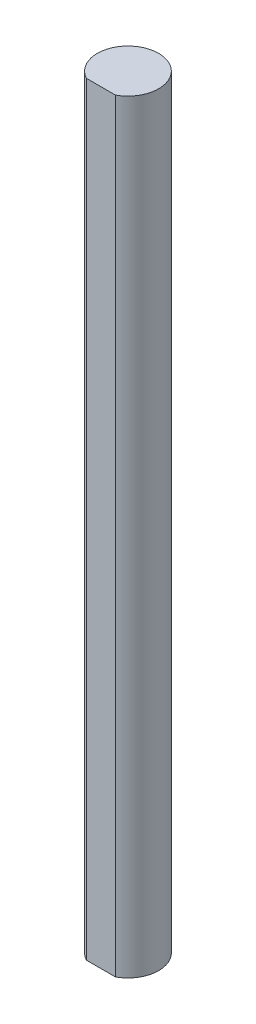
SolidWorks part; units mm, degrees
material "AISI 1045 Steel, cold drawn"
ref_plane "Front Plane" through (0, 0, 0) normal (0, 0, 1) x (1, 0, 0)
ref_plane "Top Plane" through (0, 0, 0) normal (0, 1, 0) x (1, 0, 0)
ref_plane "Right Plane" through (0, 0, 0) normal (1, 0, 0) x (0, 0, -1)
ref_axis "Axis1" through (0, -55, 0) along (0, 1, 0)
sketch "Sketch1" plane through (0, 0, 0) normal (0, 1, 0) x (1, 0, 0)
  line L0 (-1.5, -2.7983) -> (1.5, -2.7983)
  line L1 (0, 0) -> (-1.5, -2.7983) construction
  line L2 (1.5, -2.7983) -> (0, 0) construction
  line L3 (0, -55) -> (0, 55) construction
  arc A0 (1.5, -2.7983) -> (-1.5, -2.7983) centre (0, 0) ccw
  point P7 (0, -2.7983)
  dimension "D1" = 6.35
  dimension "D2" = 3
extrude "Boss-Extrude1" add sketch "Sketch1" against normal blind 79
